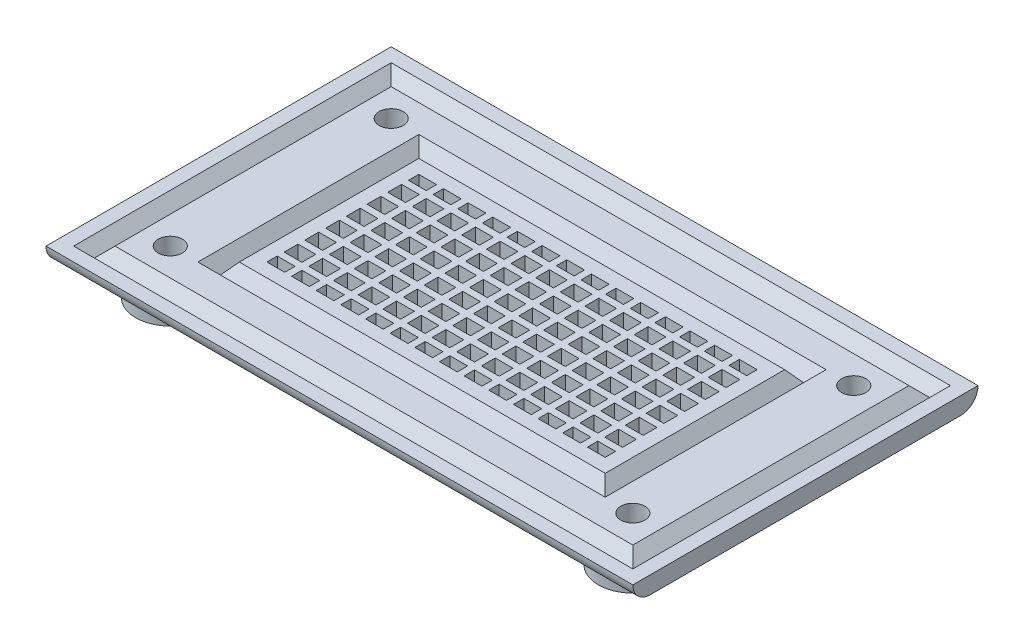
SolidWorks part; units mm, degrees
ref_plane "Front Plane" through (0, 0, 0) normal (0, 0, 1) x (1, 0, 0)
ref_plane "Top Plane" through (0, 0, 0) normal (0, 1, 0) x (1, 0, 0)
ref_plane "Right Plane" through (0, 0, 0) normal (1, 0, 0) x (0, 0, -1)
sketch "Sketch1" plane through (0, 0, 0) normal (0, 1, 0) x (1, 0, 0)
  line L1 (42.5, -25) -> (-42.5, -25)
  line L2 (42.5, -25) -> (42.5, 25)
  line L3 (42.5, 25) -> (-42.5, 25)
  line L4 (-42.5, -25) -> (-42.5, 25)
  line L5 (42.5, -25) -> (-42.5, 25) construction
  line L6 (42.5, 25) -> (-42.5, -25) construction
  point P0 (0, 0)
extrude "Base Plate" add sketch "Sketch1" along normal blind 2.5
sketch "Sketch4" plane through (0, 2.5, 0) normal (0, 1, 0) x (1, 0, 0)
  line L0 (-40.5, -23) -> (-40.5, 23)
  line L1 (-40.5, 23) -> (40.5, 23)
  line L2 (40.5, 23) -> (40.5, -23)
  line L3 (40.5, -23) -> (-40.5, -23)
  line L4 (-37.5, -20) -> (-37.5, 20)
  line L5 (-37.5, 20) -> (37.5, 20)
  line L6 (37.5, 20) -> (37.5, -20)
  line L7 (37.5, -20) -> (-37.5, -20)
  line L8 (42.5, -25) -> (42.5, 25) construction
  line L9 (-42.5, 25) -> (-42.5, -25) construction
  line L10 (-42.5, -25) -> (42.5, -25) construction
  line L11 (42.5, 25) -> (-42.5, 25) construction
  dimension "D1" = 2
  dimension "D2" = 3
  dimension "D3" = 2
  dimension "D4" = 3
  dimension "D5" = 2
  dimension "D6" = 3
  dimension "D7" = 3
  dimension "D8" = 2
extrude "Sealant Cut - Outer" cut sketch "Sketch4" against normal blind 5 draft 45
sketch "Sketch7" plane through (0, 2.5, 0) normal (0, 1, 0) x (1, 0, 0)
  line L0 (37.5, 20) -> (-37.5, 20) construction
  line L1 (-37.5, 20) -> (-37.5, -20) construction
  line L2 (0, 0) -> (-11.5051, 0) construction
  line L4 (0, 13.9859) -> (0, 0) construction
  circle A0 centre (-33.5, 16) radius 1.75
  circle A1 centre (-33.5, -16) radius 1.75
  circle A2 centre (33.5, -16) radius 1.75
  circle A3 centre (33.5, 16) radius 1.75
  dimension "D1" = 3.5
  dimension "D2" = 4
  dimension "D3" = 4
extrude "Scre Cut" cut sketch "Sketch7" against normal blind 5
sketch "Sketch12" plane through (0, 2.5, 0) normal (0, 1, 0) x (1, 0, 0)
  line L0 (29.5, -16) -> (-29.5, -16)
  line L1 (-29.5, -16) -> (-29.5, 16)
  line L2 (-29.5, 16) -> (29.5, 16)
  line L3 (29.5, 16) -> (29.5, -16)
  line L4 (26.5, -13) -> (-26.5, -13)
  line L5 (-26.5, -13) -> (-26.5, 13)
  line L6 (-26.5, 13) -> (26.5, 13)
  line L7 (26.5, 13) -> (26.5, -13)
  line L8 (37.5, 20) -> (-37.5, 20) construction
  circle A0 centre (33.5, -16) radius 1.75 construction
  circle A3 centre (-33.5, 16) radius 1.75 construction
  circle A4 centre (33.5, 16) radius 1.75 construction
  dimension "D1" = 4
  dimension "D2" = 3
  dimension "D3" = 4
  dimension "D4" = 4
  dimension "D5" = 4
  dimension "D6" = 3
  dimension "D7" = 3
  dimension "D8" = 3
extrude "Sealant Cut - Inner" cut sketch "Sketch12" against normal blind 45 draft 40
sketch "Sketch13" plane through (0, 2.5, 0) normal (0, 1, 0) x (1, 0, 0)
  line L0 (26.5, -13) -> (26.5, 13) construction
  line L1 (-24.5, 11) -> (24.5, 11)
  line L2 (-24.5, 11) -> (-24.5, -11)
  line L3 (-24.5, -11) -> (24.5, -11)
  line L4 (24.5, 11) -> (24.5, -11)
  line L5 (-24.5, 11) -> (24.5, -11) construction
  line L6 (-24.5, -11) -> (24.5, 11) construction
  line L7 (-26.5, -13) -> (26.5, -13) construction
  point P0 (0, 0)
  dimension "D1" = 2
  dimension "D2" = 2
extrude "Cut-Extrude1" cut sketch "Sketch13" against normal blind 10
sketch "Sketch14" plane through (0, 2.5, 0) normal (0, 1, 0) x (1, 0, 0)
  line L0 (-24.5, 0) -> (-22, 0) construction
  line L1 (-24.5, 11) -> (-24.5, -11) construction
  line L2 (-18.3571, -11) -> (-18.3571, -9.5)
  line L3 (-24.5, -11) -> (24.5, -11) construction
  line L4 (-21.9286, 0.5) -> (-21.9286, 2.5)
  line L5 (-24.5, -0.5) -> (-21.9286, -0.5)
  line L6 (-24.5, -0.5) -> (-24.5, 0.5)
  line L7 (-24.5, 0.5) -> (-21.9286, 0.5)
  line L8 (-20.9286, 9.5) -> (-20.9286, 11)
  line L9 (-20.9286, 6.5) -> (-20.9286, 8.5)
  line L10 (-20.9286, 3.5) -> (-20.9286, 5.5)
  line L11 (24.5, 11) -> (-24.5, 11) construction
  line L12 (-21.9286, -11) -> (-20.9286, -11)
  line L13 (-21.9286, -11) -> (-21.9286, -9.5)
  line L14 (-21.9286, 11) -> (-20.9286, 11)
  line L15 (-20.9286, -2.5) -> (-20.9286, -0.5)
  line L16 (-20.9286, -5.5) -> (-20.9286, -3.5)
  line L17 (-20.9286, -8.5) -> (-20.9286, -6.5)
  line L18 (-24.5, 2.5) -> (-24.5, 3.5)
  line L19 (-24.5, 2.5) -> (-21.9286, 2.5)
  line L20 (-24.5, 3.5) -> (-21.9286, 3.5)
  line L21 (-24.5, 5.5) -> (-24.5, 6.5)
  line L22 (-24.5, 5.5) -> (-21.9286, 5.5)
  line L23 (-24.5, 6.5) -> (-21.9286, 6.5)
  line L24 (-24.5, 8.5) -> (-24.5, 9.5)
  line L25 (-24.5, 8.5) -> (-21.9286, 8.5)
  line L26 (-24.5, 9.5) -> (-21.9286, 9.5)
  line L27 (-24.5, -3.5) -> (-21.9286, -3.5)
  line L28 (-24.5, -3.5) -> (-24.5, -2.5)
  line L29 (-24.5, -2.5) -> (-21.9286, -2.5)
  line L30 (-24.5, -6.5) -> (-21.9286, -6.5)
  line L31 (-24.5, -6.5) -> (-24.5, -5.5)
  line L32 (-24.5, -5.5) -> (-21.9286, -5.5)
  line L33 (-24.5, -9.5) -> (-21.9286, -9.5)
  line L34 (-24.5, -9.5) -> (-24.5, -8.5)
  line L35 (-24.5, -8.5) -> (-21.9286, -8.5)
  line L36 (-21.9286, -8.5) -> (-21.9286, -6.5)
  line L37 (-21.9286, -5.5) -> (-21.9286, -3.5)
  line L38 (-21.9286, -2.5) -> (-21.9286, -0.5)
  line L39 (-21.9286, 3.5) -> (-21.9286, 5.5)
  line L40 (-21.9286, 6.5) -> (-21.9286, 8.5)
  line L41 (-21.9286, 9.5) -> (-21.9286, 11)
  line L42 (-21.4286, 11) -> (-21.4286, 9.5) construction
  line L43 (-18.3571, -8.5) -> (-20.9286, -8.5)
  line L44 (-18.3571, -8.5) -> (-18.3571, -6.5)
  line L45 (-18.3571, -9.5) -> (-20.9286, -9.5)
  line L46 (-18.3571, -5.5) -> (-20.9286, -5.5)
  line L47 (-18.3571, -5.5) -> (-18.3571, -3.5)
  line L48 (-18.3571, -6.5) -> (-20.9286, -6.5)
  line L49 (-18.3571, -2.5) -> (-20.9286, -2.5)
  line L50 (-18.3571, -2.5) -> (-18.3571, -0.5)
  line L51 (-18.3571, -3.5) -> (-20.9286, -3.5)
  line L52 (-18.3571, 9.5) -> (-20.9286, 9.5)
  line L53 (-18.3571, 8.5) -> (-20.9286, 8.5)
  line L54 (-18.3571, 0.5) -> (-18.3571, 2.5)
  line L55 (-18.3571, 6.5) -> (-20.9286, 6.5)
  line L56 (-18.3571, 5.5) -> (-20.9286, 5.5)
  line L57 (-18.3571, 3.5) -> (-18.3571, 5.5)
  line L58 (-18.3571, 3.5) -> (-20.9286, 3.5)
  line L59 (-18.3571, 2.5) -> (-20.9286, 2.5)
  line L60 (-18.3571, 9.5) -> (-18.3571, 11)
  line L61 (-20.9286, -11) -> (-20.9286, -9.5)
  line L62 (-18.3571, 0.5) -> (-20.9286, 0.5)
  line L63 (-18.3571, 6.5) -> (-18.3571, 8.5)
  line L64 (-18.3571, -0.5) -> (-20.9286, -0.5)
  line L65 (-20.9286, 0.5) -> (-20.9286, 2.5)
  line L66 (-11.2143, -11) -> (-11.2143, -9.5)
  line L67 (-14.7857, 0.5) -> (-14.7857, 2.5)
  line L68 (-17.3571, -0.5) -> (-14.7857, -0.5)
  line L69 (-17.3571, 0.5) -> (-14.7857, 0.5)
  line L70 (-13.7857, 9.5) -> (-13.7857, 11)
  line L71 (-13.7857, 6.5) -> (-13.7857, 8.5)
  line L72 (-13.7857, 3.5) -> (-13.7857, 5.5)
  line L73 (-14.7857, -11) -> (-13.7857, -11)
  line L74 (-14.7857, -11) -> (-14.7857, -9.5)
  line L75 (-14.7857, 11) -> (-13.7857, 11)
  line L76 (-13.7857, -2.5) -> (-13.7857, -0.5)
  line L77 (-13.7857, -5.5) -> (-13.7857, -3.5)
  line L78 (-13.7857, -8.5) -> (-13.7857, -6.5)
  line L79 (-17.3571, 2.5) -> (-14.7857, 2.5)
  line L80 (-17.3571, 3.5) -> (-14.7857, 3.5)
  line L81 (-17.3571, 5.5) -> (-14.7857, 5.5)
  line L82 (-17.3571, 6.5) -> (-14.7857, 6.5)
  line L83 (-17.3571, 8.5) -> (-14.7857, 8.5)
  line L84 (-17.3571, 9.5) -> (-14.7857, 9.5)
  line L85 (-17.3571, -3.5) -> (-14.7857, -3.5)
  line L86 (-17.3571, -2.5) -> (-14.7857, -2.5)
  line L87 (-17.3571, -6.5) -> (-14.7857, -6.5)
  line L88 (-17.3571, -5.5) -> (-14.7857, -5.5)
  line L89 (-17.3571, -9.5) -> (-14.7857, -9.5)
  line L90 (-17.3571, -8.5) -> (-14.7857, -8.5)
  line L91 (-14.7857, -8.5) -> (-14.7857, -6.5)
  line L92 (-14.7857, -5.5) -> (-14.7857, -3.5)
  line L93 (-14.7857, -2.5) -> (-14.7857, -0.5)
  line L94 (-14.7857, 3.5) -> (-14.7857, 5.5)
  line L95 (-14.7857, 6.5) -> (-14.7857, 8.5)
  line L96 (-14.7857, 9.5) -> (-14.7857, 11)
  line L97 (-11.2143, -8.5) -> (-13.7857, -8.5)
  line L98 (-11.2143, -8.5) -> (-11.2143, -6.5)
  line L99 (-11.2143, -9.5) -> (-13.7857, -9.5)
  line L100 (-11.2143, -5.5) -> (-13.7857, -5.5)
  line L101 (-11.2143, -5.5) -> (-11.2143, -3.5)
  line L102 (-11.2143, -6.5) -> (-13.7857, -6.5)
  line L103 (-11.2143, -2.5) -> (-13.7857, -2.5)
  line L104 (-11.2143, -2.5) -> (-11.2143, -0.5)
  line L105 (-11.2143, -3.5) -> (-13.7857, -3.5)
  line L106 (-11.2143, 9.5) -> (-13.7857, 9.5)
  line L107 (-11.2143, 8.5) -> (-13.7857, 8.5)
  line L108 (-11.2143, 0.5) -> (-11.2143, 2.5)
  line L109 (-11.2143, 6.5) -> (-13.7857, 6.5)
  line L110 (-11.2143, 5.5) -> (-13.7857, 5.5)
  line L111 (-11.2143, 3.5) -> (-11.2143, 5.5)
  line L112 (-11.2143, 3.5) -> (-13.7857, 3.5)
  line L113 (-11.2143, 2.5) -> (-13.7857, 2.5)
  line L114 (-11.2143, 9.5) -> (-11.2143, 11)
  line L115 (-13.7857, -11) -> (-13.7857, -9.5)
  line L116 (-11.2143, 0.5) -> (-13.7857, 0.5)
  line L117 (-11.2143, 6.5) -> (-11.2143, 8.5)
  line L118 (-11.2143, -0.5) -> (-13.7857, -0.5)
  line L119 (-13.7857, 0.5) -> (-13.7857, 2.5)
  line L120 (-17.3571, -11) -> (-17.3571, -9.5)
  line L121 (-17.3571, 11) -> (-18.3571, 11)
  line L122 (-17.3571, 9.5) -> (-17.3571, 11)
  line L123 (-17.3571, 6.5) -> (-17.3571, 8.5)
  line L124 (-17.3571, 3.5) -> (-17.3571, 5.5)
  line L125 (-17.3571, 0.5) -> (-17.3571, 2.5)
  line L126 (-17.3571, -2.5) -> (-17.3571, -0.5)
  line L127 (-17.3571, -5.5) -> (-17.3571, -3.5)
  line L128 (-17.3571, -8.5) -> (-17.3571, -6.5)
  line L129 (-17.3571, -11) -> (-18.3571, -11)
  line L130 (-7.6429, -11) -> (-7.6429, -9.5)
  line L131 (-10.2143, 9.5) -> (-10.2143, 11)
  line L132 (-10.2143, 6.5) -> (-10.2143, 8.5)
  line L133 (-10.2143, 3.5) -> (-10.2143, 5.5)
  line L134 (-11.2143, -11) -> (-10.2143, -11)
  line L135 (-10.2143, -2.5) -> (-10.2143, -0.5)
  line L136 (-10.2143, -5.5) -> (-10.2143, -3.5)
  line L137 (-10.2143, -8.5) -> (-10.2143, -6.5)
  line L138 (-7.6429, -8.5) -> (-10.2143, -8.5)
  line L139 (-7.6429, -8.5) -> (-7.6429, -6.5)
  line L140 (-7.6429, -9.5) -> (-10.2143, -9.5)
  line L141 (-7.6429, -5.5) -> (-10.2143, -5.5)
  line L142 (-7.6429, -5.5) -> (-7.6429, -3.5)
  line L143 (-7.6429, -6.5) -> (-10.2143, -6.5)
  line L144 (-7.6429, -2.5) -> (-10.2143, -2.5)
  line L145 (-7.6429, -2.5) -> (-7.6429, -0.5)
  line L146 (-7.6429, -3.5) -> (-10.2143, -3.5)
  line L147 (-7.6429, 9.5) -> (-10.2143, 9.5)
  line L148 (-7.6429, 8.5) -> (-10.2143, 8.5)
  line L149 (-7.6429, 0.5) -> (-7.6429, 2.5)
  line L150 (-7.6429, 6.5) -> (-10.2143, 6.5)
  line L151 (-7.6429, 5.5) -> (-10.2143, 5.5)
  line L152 (-7.6429, 3.5) -> (-7.6429, 5.5)
  line L153 (-7.6429, 3.5) -> (-10.2143, 3.5)
  line L154 (-7.6429, 2.5) -> (-10.2143, 2.5)
  line L155 (-7.6429, 9.5) -> (-7.6429, 11)
  line L156 (-10.2143, -11) -> (-10.2143, -9.5)
  line L157 (-7.6429, 0.5) -> (-10.2143, 0.5)
  line L158 (-7.6429, 6.5) -> (-7.6429, 8.5)
  line L159 (-7.6429, -0.5) -> (-10.2143, -0.5)
  line L160 (-10.2143, 0.5) -> (-10.2143, 2.5)
  line L161 (-11.2143, 11) -> (-10.2143, 11)
  line L162 (-4.0714, -11) -> (-4.0714, -9.5)
  line L163 (-6.6429, 9.5) -> (-6.6429, 11)
  line L164 (-6.6429, 6.5) -> (-6.6429, 8.5)
  line L165 (-6.6429, 3.5) -> (-6.6429, 5.5)
  line L166 (-7.6429, -11) -> (-6.6429, -11)
  line L167 (-6.6429, -2.5) -> (-6.6429, -0.5)
  line L168 (-6.6429, -5.5) -> (-6.6429, -3.5)
  line L169 (-6.6429, -8.5) -> (-6.6429, -6.5)
  line L170 (-4.0714, -8.5) -> (-6.6429, -8.5)
  line L171 (-4.0714, -8.5) -> (-4.0714, -6.5)
  line L172 (-4.0714, -9.5) -> (-6.6429, -9.5)
  line L173 (-4.0714, -5.5) -> (-6.6429, -5.5)
  line L174 (-4.0714, -5.5) -> (-4.0714, -3.5)
  line L175 (-4.0714, -6.5) -> (-6.6429, -6.5)
  line L176 (-4.0714, -2.5) -> (-6.6429, -2.5)
  line L177 (-4.0714, -2.5) -> (-4.0714, -0.5)
  line L178 (-4.0714, -3.5) -> (-6.6429, -3.5)
  line L179 (-4.0714, 9.5) -> (-6.6429, 9.5)
  line L180 (-4.0714, 8.5) -> (-6.6429, 8.5)
  line L181 (-4.0714, 0.5) -> (-4.0714, 2.5)
  line L182 (-4.0714, 6.5) -> (-6.6429, 6.5)
  line L183 (-4.0714, 5.5) -> (-6.6429, 5.5)
  line L184 (-4.0714, 3.5) -> (-4.0714, 5.5)
  line L185 (-4.0714, 3.5) -> (-6.6429, 3.5)
  line L186 (-4.0714, 2.5) -> (-6.6429, 2.5)
  line L187 (-4.0714, 9.5) -> (-4.0714, 11)
  line L188 (-6.6429, -11) -> (-6.6429, -9.5)
  line L189 (-4.0714, 0.5) -> (-6.6429, 0.5)
  line L190 (-4.0714, 6.5) -> (-4.0714, 8.5)
  line L191 (-4.0714, -0.5) -> (-6.6429, -0.5)
  line L192 (-6.6429, 0.5) -> (-6.6429, 2.5)
  line L193 (-7.6429, 11) -> (-6.6429, 11)
  line L194 (-0.5, -11) -> (-0.5, -9.5)
  line L195 (-3.0714, 9.5) -> (-3.0714, 11)
  line L196 (-3.0714, 6.5) -> (-3.0714, 8.5)
  line L197 (-3.0714, 3.5) -> (-3.0714, 5.5)
  line L198 (-4.0714, -11) -> (-3.0714, -11)
  line L199 (-3.0714, -2.5) -> (-3.0714, -0.5)
  line L200 (-3.0714, -5.5) -> (-3.0714, -3.5)
  line L201 (-3.0714, -8.5) -> (-3.0714, -6.5)
  line L202 (-0.5, -8.5) -> (-3.0714, -8.5)
  line L203 (-0.5, -8.5) -> (-0.5, -6.5)
  line L204 (-0.5, -9.5) -> (-3.0714, -9.5)
  line L205 (-0.5, -5.5) -> (-3.0714, -5.5)
  line L206 (-0.5, -5.5) -> (-0.5, -3.5)
  line L207 (-0.5, -6.5) -> (-3.0714, -6.5)
  line L208 (-0.5, -2.5) -> (-3.0714, -2.5)
  line L209 (-0.5, -2.5) -> (-0.5, -0.5)
  line L210 (-0.5, -3.5) -> (-3.0714, -3.5)
  line L211 (-0.5, 9.5) -> (-3.0714, 9.5)
  line L212 (-0.5, 8.5) -> (-3.0714, 8.5)
  line L213 (-0.5, 0.5) -> (-0.5, 2.5)
  line L214 (-0.5, 6.5) -> (-3.0714, 6.5)
  line L215 (-0.5, 5.5) -> (-3.0714, 5.5)
  line L216 (-0.5, 3.5) -> (-0.5, 5.5)
  line L217 (-0.5, 3.5) -> (-3.0714, 3.5)
  line L218 (-0.5, 2.5) -> (-3.0714, 2.5)
  line L219 (-0.5, 9.5) -> (-0.5, 11)
  line L220 (-3.0714, -11) -> (-3.0714, -9.5)
  line L221 (-0.5, 0.5) -> (-3.0714, 0.5)
  line L222 (-0.5, 6.5) -> (-0.5, 8.5)
  line L223 (-0.5, -0.5) -> (-3.0714, -0.5)
  line L224 (-3.0714, 0.5) -> (-3.0714, 2.5)
  line L225 (-4.0714, 11) -> (-3.0714, 11)
  line L226 (3.0714, -11) -> (3.0714, -9.5)
  line L227 (0.5, 9.5) -> (0.5, 11)
  line L228 (0.5, 6.5) -> (0.5, 8.5)
  line L229 (0.5, 3.5) -> (0.5, 5.5)
  line L230 (-0.5, -11) -> (0.5, -11)
  line L231 (0.5, -2.5) -> (0.5, -0.5)
  line L232 (0.5, -5.5) -> (0.5, -3.5)
  line L233 (0.5, -8.5) -> (0.5, -6.5)
  line L234 (3.0714, -8.5) -> (0.5, -8.5)
  line L235 (3.0714, -8.5) -> (3.0714, -6.5)
  line L236 (3.0714, -9.5) -> (0.5, -9.5)
  line L237 (3.0714, -5.5) -> (0.5, -5.5)
  line L238 (3.0714, -5.5) -> (3.0714, -3.5)
  line L239 (3.0714, -6.5) -> (0.5, -6.5)
  line L240 (3.0714, -2.5) -> (0.5, -2.5)
  line L241 (3.0714, -2.5) -> (3.0714, -0.5)
  line L242 (3.0714, -3.5) -> (0.5, -3.5)
  line L243 (3.0714, 9.5) -> (0.5, 9.5)
  line L244 (3.0714, 8.5) -> (0.5, 8.5)
  line L245 (3.0714, 0.5) -> (3.0714, 2.5)
  line L246 (3.0714, 6.5) -> (0.5, 6.5)
  line L247 (3.0714, 5.5) -> (0.5, 5.5)
  line L248 (3.0714, 3.5) -> (3.0714, 5.5)
  line L249 (3.0714, 3.5) -> (0.5, 3.5)
  line L250 (3.0714, 2.5) -> (0.5, 2.5)
  line L251 (3.0714, 9.5) -> (3.0714, 11)
  line L252 (0.5, -11) -> (0.5, -9.5)
  line L253 (3.0714, 0.5) -> (0.5, 0.5)
  line L254 (3.0714, 6.5) -> (3.0714, 8.5)
  line L255 (3.0714, -0.5) -> (0.5, -0.5)
  line L256 (0.5, 0.5) -> (0.5, 2.5)
  line L257 (-0.5, 11) -> (0.5, 11)
  line L258 (6.6429, -11) -> (6.6429, -9.5)
  line L259 (4.0714, 9.5) -> (4.0714, 11)
  line L260 (4.0714, 6.5) -> (4.0714, 8.5)
  line L261 (4.0714, 3.5) -> (4.0714, 5.5)
  line L262 (3.0714, -11) -> (4.0714, -11)
  line L263 (4.0714, -2.5) -> (4.0714, -0.5)
  line L264 (4.0714, -5.5) -> (4.0714, -3.5)
  line L265 (4.0714, -8.5) -> (4.0714, -6.5)
  line L266 (6.6429, -8.5) -> (4.0714, -8.5)
  line L267 (6.6429, -8.5) -> (6.6429, -6.5)
  line L268 (6.6429, -9.5) -> (4.0714, -9.5)
  line L269 (6.6429, -5.5) -> (4.0714, -5.5)
  line L270 (6.6429, -5.5) -> (6.6429, -3.5)
  line L271 (6.6429, -6.5) -> (4.0714, -6.5)
  line L272 (6.6429, -2.5) -> (4.0714, -2.5)
  line L273 (6.6429, -2.5) -> (6.6429, -0.5)
  line L274 (6.6429, -3.5) -> (4.0714, -3.5)
  line L275 (6.6429, 9.5) -> (4.0714, 9.5)
  line L276 (6.6429, 8.5) -> (4.0714, 8.5)
  line L277 (6.6429, 0.5) -> (6.6429, 2.5)
  line L278 (6.6429, 6.5) -> (4.0714, 6.5)
  line L279 (6.6429, 5.5) -> (4.0714, 5.5)
  line L280 (6.6429, 3.5) -> (6.6429, 5.5)
  line L281 (6.6429, 3.5) -> (4.0714, 3.5)
  line L282 (6.6429, 2.5) -> (4.0714, 2.5)
  line L283 (6.6429, 9.5) -> (6.6429, 11)
  line L284 (4.0714, -11) -> (4.0714, -9.5)
  line L285 (6.6429, 0.5) -> (4.0714, 0.5)
  line L286 (6.6429, 6.5) -> (6.6429, 8.5)
  line L287 (6.6429, -0.5) -> (4.0714, -0.5)
  line L288 (4.0714, 0.5) -> (4.0714, 2.5)
  line L289 (3.0714, 11) -> (4.0714, 11)
  line L290 (10.2143, -11) -> (10.2143, -9.5)
  line L291 (7.6429, 9.5) -> (7.6429, 11)
  line L292 (7.6429, 6.5) -> (7.6429, 8.5)
  line L293 (7.6429, 3.5) -> (7.6429, 5.5)
  line L294 (6.6429, -11) -> (7.6429, -11)
  line L295 (7.6429, -2.5) -> (7.6429, -0.5)
  line L296 (7.6429, -5.5) -> (7.6429, -3.5)
  line L297 (7.6429, -8.5) -> (7.6429, -6.5)
  line L298 (10.2143, -8.5) -> (7.6429, -8.5)
  line L299 (10.2143, -8.5) -> (10.2143, -6.5)
  line L300 (10.2143, -9.5) -> (7.6429, -9.5)
  line L301 (10.2143, -5.5) -> (7.6429, -5.5)
  line L302 (10.2143, -5.5) -> (10.2143, -3.5)
  line L303 (10.2143, -6.5) -> (7.6429, -6.5)
  line L304 (10.2143, -2.5) -> (7.6429, -2.5)
  line L305 (10.2143, -2.5) -> (10.2143, -0.5)
  line L306 (10.2143, -3.5) -> (7.6429, -3.5)
  line L307 (10.2143, 9.5) -> (7.6429, 9.5)
  line L308 (10.2143, 8.5) -> (7.6429, 8.5)
  line L309 (10.2143, 0.5) -> (10.2143, 2.5)
  line L310 (10.2143, 6.5) -> (7.6429, 6.5)
  line L311 (10.2143, 5.5) -> (7.6429, 5.5)
  line L312 (10.2143, 3.5) -> (10.2143, 5.5)
  line L313 (10.2143, 3.5) -> (7.6429, 3.5)
  line L314 (10.2143, 2.5) -> (7.6429, 2.5)
  line L315 (10.2143, 9.5) -> (10.2143, 11)
  line L316 (7.6429, -11) -> (7.6429, -9.5)
  line L317 (10.2143, 0.5) -> (7.6429, 0.5)
  line L318 (10.2143, 6.5) -> (10.2143, 8.5)
  line L319 (10.2143, -0.5) -> (7.6429, -0.5)
  line L320 (7.6429, 0.5) -> (7.6429, 2.5)
  line L321 (6.6429, 11) -> (7.6429, 11)
  line L322 (13.7857, -11) -> (13.7857, -9.5)
  line L323 (11.2143, 9.5) -> (11.2143, 11)
  line L324 (11.2143, 6.5) -> (11.2143, 8.5)
  line L325 (11.2143, 3.5) -> (11.2143, 5.5)
  line L326 (10.2143, -11) -> (11.2143, -11)
  line L327 (11.2143, -2.5) -> (11.2143, -0.5)
  line L328 (11.2143, -5.5) -> (11.2143, -3.5)
  line L329 (11.2143, -8.5) -> (11.2143, -6.5)
  line L330 (13.7857, -8.5) -> (11.2143, -8.5)
  line L331 (13.7857, -8.5) -> (13.7857, -6.5)
  line L332 (13.7857, -9.5) -> (11.2143, -9.5)
  line L333 (13.7857, -5.5) -> (11.2143, -5.5)
  line L334 (13.7857, -5.5) -> (13.7857, -3.5)
  line L335 (13.7857, -6.5) -> (11.2143, -6.5)
  line L336 (13.7857, -2.5) -> (11.2143, -2.5)
  line L337 (13.7857, -2.5) -> (13.7857, -0.5)
  line L338 (13.7857, -3.5) -> (11.2143, -3.5)
  line L339 (13.7857, 9.5) -> (11.2143, 9.5)
  line L340 (13.7857, 8.5) -> (11.2143, 8.5)
  line L341 (13.7857, 0.5) -> (13.7857, 2.5)
  line L342 (13.7857, 6.5) -> (11.2143, 6.5)
  line L343 (13.7857, 5.5) -> (11.2143, 5.5)
  line L344 (13.7857, 3.5) -> (13.7857, 5.5)
  line L345 (13.7857, 3.5) -> (11.2143, 3.5)
  line L346 (13.7857, 2.5) -> (11.2143, 2.5)
  line L347 (13.7857, 9.5) -> (13.7857, 11)
  line L348 (11.2143, -11) -> (11.2143, -9.5)
  line L349 (13.7857, 0.5) -> (11.2143, 0.5)
  line L350 (13.7857, 6.5) -> (13.7857, 8.5)
  line L351 (13.7857, -0.5) -> (11.2143, -0.5)
  line L352 (11.2143, 0.5) -> (11.2143, 2.5)
  line L353 (10.2143, 11) -> (11.2143, 11)
  line L354 (17.3571, -11) -> (17.3571, -9.5)
  line L355 (14.7857, 9.5) -> (14.7857, 11)
  line L356 (14.7857, 6.5) -> (14.7857, 8.5)
  line L357 (14.7857, 3.5) -> (14.7857, 5.5)
  line L358 (13.7857, -11) -> (14.7857, -11)
  line L359 (14.7857, -2.5) -> (14.7857, -0.5)
  line L360 (14.7857, -5.5) -> (14.7857, -3.5)
  line L361 (14.7857, -8.5) -> (14.7857, -6.5)
  line L362 (17.3571, -8.5) -> (14.7857, -8.5)
  line L363 (17.3571, -8.5) -> (17.3571, -6.5)
  line L364 (17.3571, -9.5) -> (14.7857, -9.5)
  line L365 (17.3571, -5.5) -> (14.7857, -5.5)
  line L366 (17.3571, -5.5) -> (17.3571, -3.5)
  line L367 (17.3571, -6.5) -> (14.7857, -6.5)
  line L368 (17.3571, -2.5) -> (14.7857, -2.5)
  line L369 (17.3571, -2.5) -> (17.3571, -0.5)
  line L370 (17.3571, -3.5) -> (14.7857, -3.5)
  line L371 (17.3571, 9.5) -> (14.7857, 9.5)
  line L372 (17.3571, 8.5) -> (14.7857, 8.5)
  line L373 (17.3571, 0.5) -> (17.3571, 2.5)
  line L374 (17.3571, 6.5) -> (14.7857, 6.5)
  line L375 (17.3571, 5.5) -> (14.7857, 5.5)
  line L376 (17.3571, 3.5) -> (17.3571, 5.5)
  line L377 (17.3571, 3.5) -> (14.7857, 3.5)
  line L378 (17.3571, 2.5) -> (14.7857, 2.5)
  line L379 (17.3571, 9.5) -> (17.3571, 11)
  line L380 (14.7857, -11) -> (14.7857, -9.5)
  line L381 (17.3571, 0.5) -> (14.7857, 0.5)
  line L382 (17.3571, 6.5) -> (17.3571, 8.5)
  line L383 (17.3571, -0.5) -> (14.7857, -0.5)
  line L384 (14.7857, 0.5) -> (14.7857, 2.5)
  line L385 (13.7857, 11) -> (14.7857, 11)
  line L386 (20.9286, -11) -> (20.9286, -9.5)
  line L387 (18.3571, 9.5) -> (18.3571, 11)
  line L388 (18.3571, 6.5) -> (18.3571, 8.5)
  line L389 (18.3571, 3.5) -> (18.3571, 5.5)
  line L390 (17.3571, -11) -> (18.3571, -11)
  line L391 (18.3571, -2.5) -> (18.3571, -0.5)
  line L392 (18.3571, -5.5) -> (18.3571, -3.5)
  line L393 (18.3571, -8.5) -> (18.3571, -6.5)
  line L394 (20.9286, -8.5) -> (18.3571, -8.5)
  line L395 (20.9286, -8.5) -> (20.9286, -6.5)
  line L396 (20.9286, -9.5) -> (18.3571, -9.5)
  line L397 (20.9286, -5.5) -> (18.3571, -5.5)
  line L398 (20.9286, -5.5) -> (20.9286, -3.5)
  line L399 (20.9286, -6.5) -> (18.3571, -6.5)
  line L400 (20.9286, -2.5) -> (18.3571, -2.5)
  line L401 (20.9286, -2.5) -> (20.9286, -0.5)
  line L402 (20.9286, -3.5) -> (18.3571, -3.5)
  line L403 (20.9286, 9.5) -> (18.3571, 9.5)
  line L404 (20.9286, 8.5) -> (18.3571, 8.5)
  line L405 (20.9286, 0.5) -> (20.9286, 2.5)
  line L406 (20.9286, 6.5) -> (18.3571, 6.5)
  line L407 (20.9286, 5.5) -> (18.3571, 5.5)
  line L408 (20.9286, 3.5) -> (20.9286, 5.5)
  line L409 (20.9286, 3.5) -> (18.3571, 3.5)
  line L410 (20.9286, 2.5) -> (18.3571, 2.5)
  line L411 (20.9286, 9.5) -> (20.9286, 11)
  line L412 (18.3571, -11) -> (18.3571, -9.5)
  line L413 (20.9286, 0.5) -> (18.3571, 0.5)
  line L414 (20.9286, 6.5) -> (20.9286, 8.5)
  line L415 (20.9286, -0.5) -> (18.3571, -0.5)
  line L416 (18.3571, 0.5) -> (18.3571, 2.5)
  line L417 (17.3571, 11) -> (18.3571, 11)
  line L418 (24.5, -6.5) -> (24.5, -5.5)
  line L419 (21.9286, 9.5) -> (21.9286, 11)
  line L420 (21.9286, 6.5) -> (21.9286, 8.5)
  line L421 (21.9286, 3.5) -> (21.9286, 5.5)
  line L422 (20.9286, -11) -> (21.9286, -11)
  line L423 (21.9286, -2.5) -> (21.9286, -0.5)
  line L424 (21.9286, -5.5) -> (21.9286, -3.5)
  line L425 (21.9286, -8.5) -> (21.9286, -6.5)
  line L426 (24.5, -8.5) -> (21.9286, -8.5)
  line L427 (24.5, -3.5) -> (24.5, -2.5)
  line L428 (24.5, -9.5) -> (21.9286, -9.5)
  line L429 (24.5, -5.5) -> (21.9286, -5.5)
  line L430 (24.5, -0.5) -> (24.5, 0.5)
  line L431 (24.5, -6.5) -> (21.9286, -6.5)
  line L432 (24.5, -2.5) -> (21.9286, -2.5)
  line L433 (24.5, 8.5) -> (24.5, 9.5)
  line L434 (24.5, -3.5) -> (21.9286, -3.5)
  line L435 (24.5, 9.5) -> (21.9286, 9.5)
  line L436 (24.5, 8.5) -> (21.9286, 8.5)
  line L437 (24.5, 5.5) -> (24.5, 6.5)
  line L438 (24.5, 6.5) -> (21.9286, 6.5)
  line L439 (24.5, 5.5) -> (21.9286, 5.5)
  line L440 (24.5, 2.5) -> (24.5, 3.5)
  line L441 (24.5, 3.5) -> (21.9286, 3.5)
  line L442 (24.5, 2.5) -> (21.9286, 2.5)
  line L443 (24.5, -11) -> (24.5, 11) construction
  line L444 (21.9286, -11) -> (21.9286, -9.5)
  line L445 (24.5, 0.5) -> (21.9286, 0.5)
  line L447 (24.5, -0.5) -> (21.9286, -0.5)
  line L448 (21.9286, 0.5) -> (21.9286, 2.5)
  line L449 (20.9286, 11) -> (21.9286, 11)
  line L451 (24.5, -9.5) -> (24.5, -8.5)
  line L454 (24.5, -11) -> (24.5, -9.5) [skipped]
  line L455 (24.5, -8.5) -> (24.5, -6.5) [skipped]
  line L456 (24.5, -5.5) -> (24.5, -3.5) [skipped]
  line L457 (24.5, -2.5) -> (24.5, -0.5) [skipped]
  line L458 (24.5, 9.5) -> (24.5, 11) [skipped]
  line L459 (24.5, 6.5) -> (24.5, 8.5) [skipped]
  line L460 (24.5, 3.5) -> (24.5, 5.5) [skipped]
  line L461 (24.5, 0.5) -> (24.5, 2.5) [skipped]
  dimension "D1" = 1
  dimension "D2" = 1
  dimension "D6" = 2
  dimension "D7" = 11
  dimension "D8" = 1
  dimension "D4" = 4
  dimension "D5" = 4
extrude "Boss-Extrude1" add sketch "Sketch14" against normal up to surface (2.5 mm away) up to face at (0, 0, 0)
sketch "Sketch15" plane through (-42.5, 0, -25) normal (0, -1, 0) x (1, 0, 0)
  line L0 (42.5, 0) -> (42.5, 50) construction
  line L1 (85, 0) -> (0, 0) construction
  line L2 (0, 0) -> (0, 50) construction
  line L3 (0, 25) -> (42.5, 25) construction
  circle A0 centre (9, 9) radius 5
  circle A1 centre (9, 41) radius 5
  circle A2 centre (76, 41) radius 5
  circle A3 centre (76, 9) radius 5
  dimension "D1" = 10
extrude "Boss-Extrude3" add sketch "Sketch15" along normal blind 4
sketch "Sketch18" plane through (0, 0, 0) normal (0, 1, 0) x (1, 0, 0)
  line L0 (0, 0) -> (0, -29.8583) construction
  line L2 (-49.7998, 0) -> (0, 0) construction
  circle A0 centre (-33.5, 16) radius 1.75
  circle A1 centre (-33.5, 16) radius 1.75 construction
  circle A2 centre (-33.5, -16) radius 1.75
  circle A3 centre (33.5, 16) radius 1.75
  circle A4 centre (33.5, -16) radius 1.75
extrude "Cut-Extrude4" cut sketch "Sketch18" against normal up to surface (4 mm away) up to face at (-33.5, -4, -21)
sketch "Sketch19" plane through (0, -4, 0) normal (0, -1, 0) x (1, 0, 0)
  line L0 (0, 0) -> (0, -22.785) construction
  line L1 (-33.5, -12.7668) -> (-36.3, -14.3834)
  line L2 (-36.3, -14.3834) -> (-36.3, -17.6166)
  line L3 (-36.3, -17.6166) -> (-33.5, -19.2332)
  line L4 (-33.5, -19.2332) -> (-30.7, -17.6166)
  line L5 (-30.7, -17.6166) -> (-30.7, -14.3834)
  line L6 (-30.7, -14.3834) -> (-33.5, -12.7668)
  line L7 (-30.7, 14.3834) -> (-33.5, 12.7668)
  line L8 (-38.1664, 0) -> (0, 0) construction
  line L9 (-30.7, 17.6166) -> (-30.7, 14.3834)
  line L10 (-33.5, 19.2332) -> (-30.7, 17.6166)
  line L11 (-36.3, 17.6166) -> (-33.5, 19.2332)
  line L12 (-36.3, 14.3834) -> (-36.3, 17.6166)
  line L13 (-33.5, 12.7668) -> (-36.3, 14.3834)
  line L14 (30.7, -14.3834) -> (33.5, -12.7668)
  line L15 (30.7, -17.6166) -> (30.7, -14.3834)
  line L16 (33.5, -19.2332) -> (30.7, -17.6166)
  line L17 (36.3, -17.6166) -> (33.5, -19.2332)
  line L18 (36.3, -14.3834) -> (36.3, -17.6166)
  line L19 (33.5, -12.7668) -> (36.3, -14.3834)
  line L20 (33.5, 12.7668) -> (36.3, 14.3834)
  line L21 (36.3, 14.3834) -> (36.3, 17.6166)
  line L22 (36.3, 17.6166) -> (33.5, 19.2332)
  line L23 (33.5, 19.2332) -> (30.7, 17.6166)
  line L24 (30.7, 17.6166) -> (30.7, 14.3834)
  line L25 (30.7, 14.3834) -> (33.5, 12.7668)
  circle A2 centre (-33.5, -16) radius 2.8 construction
  circle A3 centre (-33.5, 16) radius 2.8 construction
  circle A4 centre (33.5, -16) radius 2.8 construction
  circle A5 centre (33.5, 16) radius 2.8 construction
  dimension "D1" = 5.6
extrude "M3 Nut" cut sketch "Sketch19" against normal blind 3
fillet "Fillet1" radius 2.5 1 edges at (0, 0, -25) type face fillet first side face at (33.5, 0, 21) second side face at (0, 1.25, -25)
fillet "Fillet2" radius 2.5 1 edges at (0, 0, 25) type face fillet first side face at (33.5, 0, 21) second side face at (0, 1.25, 25)
